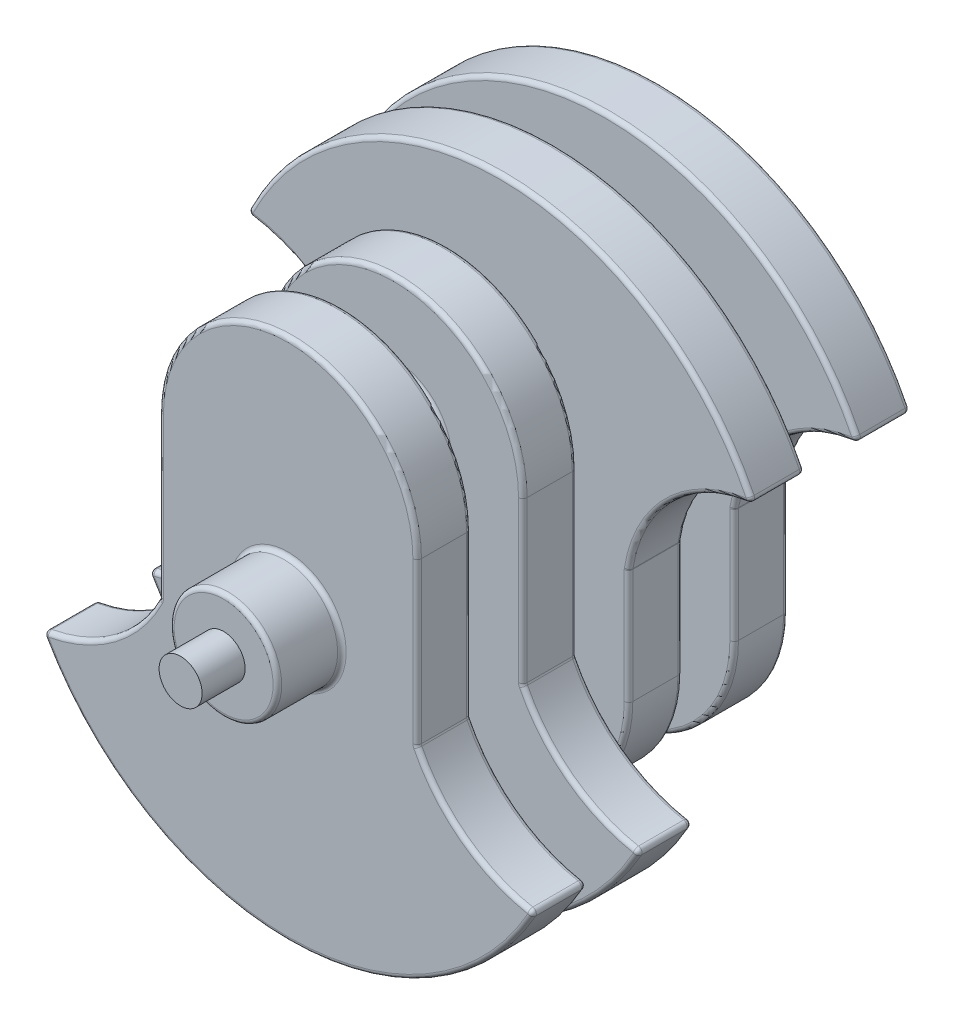
SolidWorks part; units mm, degrees
material "AISI 4340 Steel, normalized"
ref_plane "Front Plane" through (0, 0, 0) normal (0, 0, 1) x (1, 0, 0)
ref_plane "Top Plane" through (0, 0, 0) normal (0, 1, 0) x (1, 0, 0)
ref_plane "Right Plane" through (0, 0, 0) normal (1, 0, 0) x (0, 0, -1)
sketch "Sketch1" plane through (0, 0, 0) normal (0, 0, 1) x (1, 0, 0)
  circle A0 centre (0, 0) radius 25
  dimension "D1" = 25
extrude "Boss-Extrude1" add sketch "Sketch1" along normal blind 30
sketch "Sketch8" plane through (0, 0, 0) normal (0, 0, -1) x (-1, 0, 0)
  line L0 (-60, 53.333) -> (-60, -21.6543)
  line L1 (60, 53.333) -> (60, -21.6543)
  arc A0 (60, 53.333) -> (-60, 53.333) centre (0, 53.333) ccw
  arc A5 (-114.5147, -61.5336) -> (114.5147, -61.5336) centre (0, 0) ccw
  arc A6 (-60, -21.6543) -> (-114.5147, -61.5336) centre (-125, 10) cw
  arc A7 (60, -21.6543) -> (114.5147, -61.5336) centre (125, 10) ccw
  dimension "D1" = 60
  dimension "D2" = 130
  dimension "D3" = 53.333
  dimension "D5" = 10
  dimension "D6" = 125
extrude "Boss-Extrude5" add sketch "Sketch8" along normal blind 25
sketch "Sketch2" plane through (0, 0, 30) normal (0, 0, 1) x (1, 0, 0)
  circle A0 centre (0, 0) radius 10
  dimension "D1" = 10
extrude "Boss-Extrude2" add sketch "Sketch2" along normal blind 20
sketch "Sketch9" plane through (0, 0, -25) normal (0, 0, -1) x (-1, 0, 0)
  circle A0 centre (0, 53.333) radius 25
  dimension "D2" = 25
  dimension "D1" = 53.333
extrude "Boss-Extrude6" add sketch "Sketch9" along normal blind 24.13
ref_plane "Plane4" through (0, 0, -98.26) normal (0, 0, -1) x (-1, 0, 0)
sketch "Sketch10" plane through (0, 0, -49.13) normal (0, 0, -1) x (-1, 0, 0)
  line L0 (-60, -53.333) -> (-60, 0)
  line L1 (60, -53.333) -> (60, 0)
  arc A0 (-60, -53.333) -> (60, -53.333) centre (0, -53.333) ccw
  arc A1 (-60, 0) -> (-117.628, 55.3502) centre (-125, -10) ccw
  arc A2 (60, 0) -> (117.628, 55.3502) centre (125, -10) cw
  arc A3 (-117.628, 55.3502) -> (117.628, 55.3502) centre (0, 0) cw
  dimension "D1" = 60
  dimension "D5" = 10
  dimension "D3" = 130
  dimension "D2" = 53.333
  dimension "D4" = 125
extrude "Boss-Extrude7" add sketch "Sketch10" along normal blind 25 from surface starting at plane "Plane4"
ref_plane "Plane3" through (0, 0, -147.39) normal (0, 0, -1) x (-1, 0, 0)
sketch "Sketch12" plane through (0, 0, -147.39) normal (0, 0, -1) x (-1, 0, 0)
  line L2 (60, -53.333) -> (60, 0)
  line L3 (60, -53.333) -> (60, 0)
  line L4 (-60, 0) -> (-60, -53.333)
  line L5 (-60, 0) -> (-60, -53.333)
  arc A12 (-60, -53.333) -> (60, -53.333) centre (0, -53.333) ccw
  arc A13 (117.628, 55.3502) -> (60, 0) centre (125, -10) ccw
  arc A14 (117.628, 55.3502) -> (-117.628, 55.3502) centre (0, 0) ccw
  arc A15 (-60, 0) -> (-117.628, 55.3502) centre (-125, -10) ccw
  arc A16 (-60, -53.333) -> (60, -53.333) centre (0, -53.333) ccw
  arc A17 (117.628, 55.3502) -> (60, 0) centre (125, -10) ccw
  arc A18 (117.628, 55.3502) -> (-117.628, 55.3502) centre (0, 0) ccw
  arc A19 (-60, 0) -> (-117.628, 55.3502) centre (-125, -10) ccw
  dimension "D1" = 0
extrude "Boss-Extrude8" add sketch "Sketch12" along normal blind 25
sketch "Sketch14" plane through (0, 0, -123.26) normal (0, 0, -1) x (-1, 0, 0)
  circle A0 centre (0, -53.333) radius 25
  dimension "D2" = 25
  dimension "D1" = 53.333
extrude "Boss-Extrude9" add sketch "Sketch14" along normal up to next
sketch "Sketch15" plane through (0, 0, -172.39) normal (0, 0, -1) x (-1, 0, 0)
  circle A1 centre (0, 0) radius 25
  circle A2 centre (0, 0) radius 25
  dimension "D1" = 0
extrude "Boss-Extrude10" add sketch "Sketch15" along normal blind 30
sketch "Sketch16" plane through (0, 0, -202.39) normal (0, 0, -1) x (-1, 0, 0)
  circle A1 centre (0, 0) radius 10
  circle A2 centre (0, 0) radius 10
  dimension "D1" = 0
extrude "Boss-Extrude11" add sketch "Sketch16" along normal blind 20
sketch "Sketch18" plane through (0, 0, -49.13) normal (0, 0, -1) x (-1, 0, 0)
  line L2 (-60, 53.333) -> (-60, -21.6543)
  line L3 (-60, 53.333) -> (-60, -21.6543)
  line L4 (60, -21.6543) -> (60, 53.333)
  line L5 (60, -21.6543) -> (60, 53.333)
  arc A4 (60, 53.333) -> (-60, 53.333) centre (0, 53.333) ccw
  arc A5 (-114.5147, -61.5336) -> (-60, -21.6543) centre (-125, 10) ccw
  arc A6 (-114.5147, -61.5336) -> (114.5147, -61.5336) centre (0, 0) ccw
  arc A7 (60, -21.6543) -> (114.5147, -61.5336) centre (125, 10) ccw
  arc A8 (60, 53.333) -> (-60, 53.333) centre (0, 53.333) ccw
  arc A9 (-114.5147, -61.5336) -> (-60, -21.6543) centre (-125, 10) ccw
  arc A10 (-114.5147, -61.5336) -> (114.5147, -61.5336) centre (0, 0) ccw
  arc A11 (60, -21.6543) -> (114.5147, -61.5336) centre (125, 10) ccw
  dimension "D1" = 0
extrude "Boss-Extrude12" add sketch "Sketch18" along normal blind 25
sketch "Sketch19" plane through (0, 0, -74.13) normal (0, 0, -1) x (-1, 0, 0)
  circle A1 centre (0, 0) radius 25
  circle A2 centre (0, 0) radius 25
  dimension "D1" = 0
extrude "Boss-Extrude13" add sketch "Sketch19" along normal up to next
fillet "Fillet1" radius 2 32 edges at (0, -130, -49.13) (-82.314, -48.3515, -49.13) (-60, 15.8394, -49.13) (60, 15.8394, -49.13) (82.314, -48.3515, -49.13) (0, -130, -74.13) (-82.314, -48.3515, -74.13) (-60, 15.8394, -74.13) (0, 113.333, -74.13) (60, 15.8394, -74.13) (82.314, -48.3515, -74.13) (114.5147, -61.5336, -61.63) (60, -21.6543, -61.63) (-60, -21.6543, -61.63) (-114.5147, -61.5336, -61.63) (0, 113.333, -49.13) (60, 15.8394, 0) (82.314, -48.3515, 0) (0, -130, 0) (-82.314, -48.3515, 0) (-60, 15.8394, 0) (0, 113.333, -25) (60, 15.8394, -25) (82.314, -48.3515, -25) (0, -130, -25) (-82.314, -48.3515, -25) (-60, 15.8394, -25) (-60, -21.6543, -12.5) (-114.5147, -61.5336, -12.5) (114.5147, -61.5336, -12.5) (60, -21.6543, -12.5) (0, 113.333, 0)
fillet "Fillet2" radius 2 16 edges at (0, 130, -147.39) (79.4441, 37.4306, -147.39) (60, -26.6665, -147.39) (0, -113.333, -147.39) (-60, -26.6665, -147.39) (-79.4441, 37.4306, -147.39) (79.4441, 37.4306, -172.39) (60, -26.6665, -172.39) (0, -113.333, -172.39) (-60, -26.6665, -172.39) (-79.4441, 37.4306, -172.39) (-117.628, 55.3502, -159.89) (-60, 0, -159.89) (60, 0, -159.89) (117.628, 55.3502, -159.89) (0, 130, -172.39)
fillet "Fillet3" radius 2 16 edges at (60, -26.6665, -98.26) (79.4441, 37.4306, -98.26) (0, 130, -98.26) (-79.4441, 37.4306, -98.26) (-60, -26.6665, -98.26) (0, -113.333, -98.26) (60, -26.6665, -123.26) (79.4441, 37.4306, -123.26) (-79.4441, 37.4306, -123.26) (-60, -26.6665, -123.26) (0, -113.333, -123.26) (60, 0, -110.76) (117.628, 55.3502, -110.76) (-117.628, 55.3502, -110.76) (-60, 0, -110.76) (0, 130, -123.26)
fillet "Fillet5" radius 2 2 edges at (25, 0, 30) (25, 0, 0)
fillet "Fillet6" radius 2 2 edges at (-25, 0, -172.39) (-25, 0, -202.39)
ref_plane "Plane5" through (0, 20, 0) normal (0, 1, 0) x (1, 0, 0)
sketch "Sketch20" plane through (0, 0, 0) normal (1, 0, 0) x (0, 0, -1)
  line L1 (123.26, -78.333) -> (123.26, -28.333)
  line L2 (123.26, -78.333) -> (123.26, -28.333)
  dimension "D1" = 0
ref_plane "Plane6" through (0, -78.333, 0) normal (0, 1, 0) x (1, 0, 0)
sketch "Sketch21" plane through (0, 20, 0) normal (0, 1, 0) x (1, 0, 0)
  line L2 (-25, 200.39) -> (25, 200.39) construction
  line L3 (-25, 200.39) -> (-25, 174.39) construction
  line L4 (-25, 174.39) -> (25, 174.39) construction
  line L5 (25, 200.39) -> (25, 174.39) construction
  circle A0 centre (0, 187.39) radius 2.5
  point P10 (0, 200.39)
  point P11 (25, 187.39)
  dimension "D1" = 5
sketch "Sketch27" plane through (0, 0, 0) normal (0, 0, 1) x (1, 0, 0)
  line L0 (0, 78.333) -> (0, -25) construction
  circle A1 centre (0, 53.333) radius 25
  circle A2 centre (0, 53.333) radius 25 construction
  circle A3 centre (0, 0) radius 25
  circle A4 centre (0, 0) radius 25 construction
  dimension "D1" = 0
  dimension "D2" = 0
ref_plane "Plane8" through (0, 78.333, 0) normal (0, -1, 0) x (-1, 0, 0)
ref_plane "Plane9" through (0, -25, 0) normal (0, -1, 0) x (-1, 0, 0)
sketch "Sketch28" plane through (0, -25, 0) normal (0, -1, 0) x (-1, 0, 0)
  line L1 (-25, -2) -> (25, -2) construction
  line L2 (-25, -2) -> (-25, -28) construction
  line L3 (-25, -28) -> (25, -28) construction
  line L4 (25, -2) -> (25, -28) construction
  line L5 (-25, -2) -> (25, -28) construction
  line L6 (-25, -28) -> (25, -2) construction
  circle A0 centre (0, -15) radius 2.5
  point P4 (0, -15)
  dimension "D1" = 5
sketch "Sketch29" plane through (0, 78.333, 0) normal (0, -1, 0) x (-1, 0, 0)
  line L1 (25, 49.13) -> (-25, 49.13) construction
  line L2 (25, 49.13) -> (25, 25) construction
  line L3 (25, 25) -> (-25, 25) construction
  line L4 (-25, 49.13) -> (-25, 25) construction
  line L5 (25, 49.13) -> (-25, 25) construction
  line L6 (25, 25) -> (-25, 49.13) construction
  circle A0 centre (0, 37.065) radius 2.5
  point P4 (0, 37.065)
  dimension "D1" = 5
sketch "Sketch31" plane through (0, 0, 0) normal (1, 0, 0) x (0, 0, -1)
  line L0 (37.065, 78.333) -> (-15, -25) construction
ref_plane "Plane10" through (0, 78.333, -37.065) normal (0, -0.893, 0.45) x (-1, 0, 0)
hole_wizard "#26 (0.147) Diameter Hole2" positions "Sketch34" profile "Sketch35" hole size "#26" standard "ANSI Inch"
sketch "Sketch34" plane through (0, 78.333, -37.065) normal (0, -0.893, 0.45) x (-1, 0, 0)
  point P0 (0, 0)
sketch "Sketch35" plane through (0, 78.333, -37.065) normal (1, 0, 0) x (0, 0.45, 0.893)
  line L0 (0, 0) -> (0, 122.6802)
  line L1 (0, 122.6802) -> (1.8669, 121.5585)
  line L2 (1.8669, 121.5585) -> (1.8669, 0.635)
  line L3 (1.8669, 0.635) -> (2.5019, 0)
  line L5 (2.5019, 0) -> (0, 0)
  line L6 (-1.8669, 0.635) -> (-2.5019, 0) construction
  line L10 (0, 122.6802) -> (-1.8669, 121.5585) construction
  line L11 (0, -6.35) -> (0, 107.95) construction
  dimension "Hole Dia." = 3.7338
  dimension "Hole Depth" = 121.5585
  dimension "Near C'Sink Dia." = 5.0038
  dimension "Near C'Sink Angle" = 90
  dimension "Drill Angle" = 118
ref_plane "Plane11" through (0, -25, 15) normal (0, -0.893, 0.45) x (-1, 0, 0)
hole_wizard "#26 (0.147) Diameter Hole1" positions "Sketch37" profile "Sketch38" hole size "#26" standard "ANSI Inch"
sketch "Sketch37" plane through (0, -25, 15) normal (0, -0.893, 0.45) x (-1, 0, 0)
  point P0 (0, 0)
sketch "Sketch38" plane through (0, -25, 15) normal (1, 0, 0) x (0, -0.45, -0.893)
  line L0 (0, 0) -> (0, 121.1217)
  line L1 (0, 121.1217) -> (1.8669, 120)
  line L2 (1.8669, 120) -> (1.8669, 0.635)
  line L3 (1.8669, 0.635) -> (2.5019, 0)
  line L5 (2.5019, 0) -> (0, 0)
  line L6 (-1.8669, 0.635) -> (-2.5019, 0) construction
  line L10 (0, 121.1217) -> (-1.8669, 120) construction
  line L11 (0, -6.35) -> (0, 107.95) construction
  dimension "Hole Dia." = 3.7338
  dimension "Hole Depth" = 120
  dimension "Near C'Sink Dia." = 5.0038
  dimension "Near C'Sink Angle" = 90
  dimension "Drill Angle" = 118
combine bodies "Combine1" operation type add bodies to combine 123 109 117
fillet "Fillet7" radius 2 6 edges at (-25, 53.333, -49.13) (-25, 53.333, -25) (-25, 0, -74.13) (-25, 0, -98.26) (-25, -53.333, -147.39) (-25, -53.333, -123.26)
sketch "Sketch39" plane through (0, -78.333, 0) normal (0, 1, 0) x (1, 0, 0)
  line L1 (25, 145.39) -> (-25, 145.39) construction
  line L2 (25, 145.39) -> (25, 125.26) construction
  line L3 (25, 125.26) -> (-25, 125.26) construction
  line L4 (-25, 145.39) -> (-25, 125.26) construction
  line L5 (25, 145.39) -> (-25, 125.26) construction
  line L6 (25, 125.26) -> (-25, 145.39) construction
  point P4 (0, 135.325)
sketch "Sketch40" plane through (0, 0, 0) normal (1, 0, 0) x (0, 0, -1)
  line L0 (187.39, 20) -> (135.325, -78.333) construction
  line L1 (200.39, 20) -> (174.39, 20) construction
  point P5 (0, 0)
ref_plane "Plane12" through (0, 20, -187.39) normal (0, -0.8838, 0.4679) x (-1, 0, 0)
hole_wizard "#26 (0.147) Diameter Hole3" positions "Sketch42" profile "Sketch43" hole size "#26" standard "ANSI Inch"
sketch "Sketch42" plane through (0, 20, -187.39) normal (0, -0.8838, 0.4679) x (-1, 0, 0)
  point P0 (0, 0)
sketch "Sketch43" plane through (0, 20, -187.39) normal (1, 0, 0) x (0, 0.4679, 0.8838)
  line L0 (0, 0) -> (0, 121.1217)
  line L1 (0, 121.1217) -> (1.8669, 120)
  line L2 (1.8669, 120) -> (1.8669, 0.635)
  line L3 (1.8669, 0.635) -> (2.5019, 0)
  line L5 (2.5019, 0) -> (0, 0)
  line L6 (-1.8669, 0.635) -> (-2.5019, 0) construction
  line L10 (0, 121.1217) -> (-1.8669, 120) construction
  line L11 (0, -6.35) -> (0, 107.95) construction
  dimension "Hole Dia." = 3.7338
  dimension "Hole Depth" = 120
  dimension "Near C'Sink Dia." = 5.0038
  dimension "Near C'Sink Angle" = 90
  dimension "Drill Angle" = 118
ref_plane "Plane13" through (0, -78.333, -135.325) normal (0, -0.8838, 0.4679) x (-1, 0, 0)
hole_wizard "#26 (0.147) Diameter Hole4" positions "Sketch44" profile "Sketch45" hole size "#26" standard "ANSI Inch" end condition through all
sketch "Sketch44" plane through (0, -78.333, -135.325) normal (0, -0.8838, 0.4679) x (-1, 0, 0)
  point P0 (0, 0)
sketch "Sketch45" plane through (0, -78.333, -135.325) normal (1, 0, 0) x (0, -0.4679, -0.8838)
  line L0 (0, 0) -> (0, 224.8578)
  line L1 (0, 224.8578) -> (1.8669, 224.8578)
  line L2 (1.8669, 224.8578) -> (1.8669, 0.635)
  line L3 (1.8669, 0.635) -> (2.5019, 0)
  line L5 (2.5019, 0) -> (0, 0)
  line L6 (-1.8669, 0.635) -> (-2.5019, 0) construction
  line L11 (0, -6.35) -> (0, 107.95) construction
  dimension "Thru Hole Dia." = 3.7338
  dimension "Thru Hole Depth" = 224.8578
  dimension "Near C'Sink Dia." = 5.0038
  dimension "Near C'Sink Angle" = 90
equation "\"Crank Radius\"= 53.333mm"
equation "\"D1@Sketch9\"=\"Crank Radius\""
equation "\"D1@Sketch14\"=\"Crank Radius\""
equation "\"Journal Radius\" = 25mm"
equation "\"D1@Sketch1\"=\"Journal Radius\""
equation "\"D2@Sketch9\"=\"Journal Radius\""
equation "\"D2@Sketch14\"=\"Journal Radius\""
equation "\"Lobe Thickness\"= 25mm"
equation "\"D1@Boss-Extrude5\"=\"Lobe Thickness\""
equation "\"D1@Boss-Extrude7\"=\"Lobe Thickness\""
equation "\"D1@Boss-Extrude8\"=\"Lobe Thickness\""
equation "\"D1@Boss-Extrude12\"=\"Lobe Thickness\""
equation "\"D3@Sketch8\"=\"Crank Radius\""
equation "\"D2@Sketch10\"=\"Crank Radius\""
